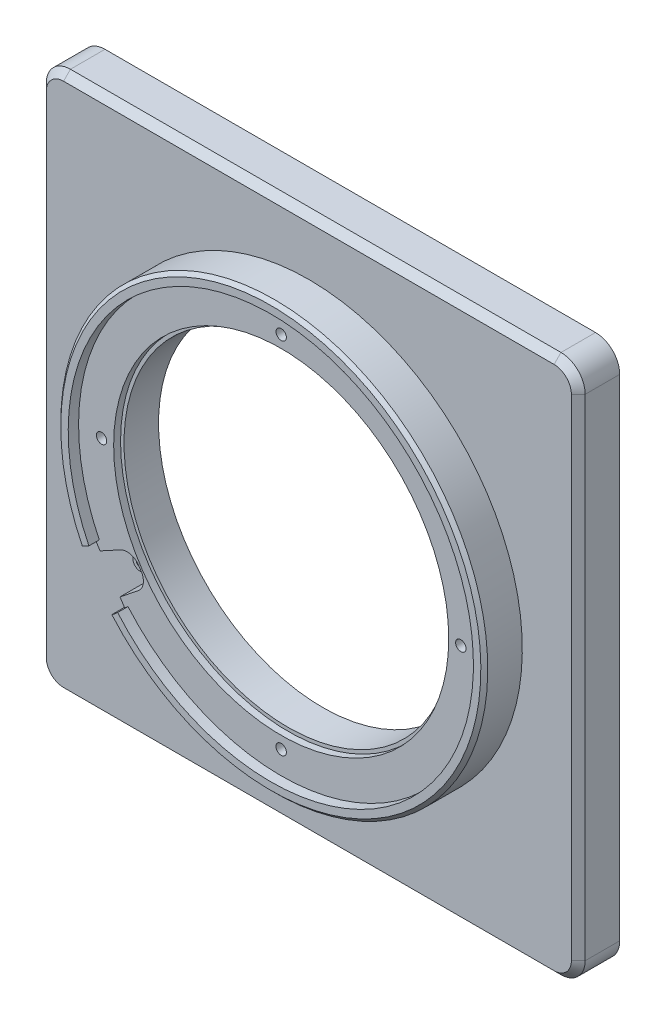
SolidWorks part; units mm, degrees
ref_plane "前视基准面" through (0, 0, 0) normal (0, 0, 1) x (1, 0, 0)
ref_plane "上视基准面" through (0, 0, 0) normal (0, 1, 0) x (1, 0, 0)
ref_plane "右视基准面" through (0, 0, 0) normal (1, 0, 0) x (0, 0, -1)
other "Configuration Table"
sketch "草图1" plane through (0, 0, 0) normal (0, 0, 1) x (1, 0, 0)
  line L1 (-39, -39) -> (39, -39)
  line L2 (-39, -39) -> (-39, 39)
  line L3 (-39, 39) -> (39, 39)
  line L4 (39, -39) -> (39, 39)
  line L5 (-39, -39) -> (39, 39) construction
  line L6 (-39, 39) -> (39, -39) construction
  circle A0 centre (0, 0) radius 23.75
  point P0 (0, 0)
  dimension "D2" = 47.5
  dimension "D1" = 78
extrude "凸台-拉伸1" add sketch "草图1" against normal blind 2
sketch "草图2" plane through (0, 0, 0) normal (0, 0, 1) x (1, 0, 0)
  circle A0 centre (0, 0) radius 23.75
  circle A1 centre (0, 0) radius 23.75 construction
  circle A2 centre (0, 0) radius 30.9
  dimension "D1" = 61.8
extrude "凸台-拉伸2" add sketch "草图2" along normal blind 4
sketch "草图3" plane through (0, 0, -2) normal (0, 0, -1) x (-1, 0, 0)
  line L1 (-39, -39) -> (39, -39)
  line L2 (-39, -39) -> (-39, 39)
  line L3 (-39, 39) -> (39, 39)
  line L4 (39, -39) -> (39, 39)
  line L5 (-39, -39) -> (39, 39) construction
  line L6 (-39, 39) -> (39, -39) construction
  line L7 (-37, -37) -> (37, -37)
  line L8 (-37, -37) -> (-37, 37)
  line L9 (-37, 37) -> (37, 37)
  line L10 (37, -37) -> (37, 37)
  line L11 (-37, -37) -> (37, 37) construction
  line L12 (-37, 37) -> (37, -37) construction
  line L13 (-37, 37) -> (-32, 37)
  line L14 (-37, 37) -> (-37, 32)
  line L15 (-37, 32) -> (-32, 32)
  line L16 (-32, 37) -> (-32, 32)
  line L17 (37, 37) -> (32, 37)
  line L18 (37, 37) -> (37, 32)
  line L19 (37, 32) -> (32, 32)
  line L20 (32, 37) -> (32, 32)
  line L21 (-37, -37) -> (-32, -37)
  line L22 (-37, -37) -> (-37, -32)
  line L23 (-37, -32) -> (-32, -32)
  line L24 (-32, -37) -> (-32, -32)
  line L25 (37, -37) -> (32, -37)
  line L26 (37, -37) -> (37, -32)
  line L27 (37, -32) -> (32, -32)
  line L28 (32, -37) -> (32, -32)
  point P0 (0, 0)
  point P7 (0, 0)
  line M23 (-39, 39) -> (-39, -39)
  line M24 (-39, -39) -> (39, -39)
  line M25 (39, -39) -> (39, 39)
  line M26 (39, 39) -> (-39, 39)
  dimension "D1" = 2
  dimension "D2" = 5
extrude "凸台-拉伸3" add sketch "草图3" along normal blind 4 contours L10 L7 L8 L9 M26 M23 M24 M25 | L16 L9 L8 L15 | L9 L20 L19 L10 | L28 L7 L10 L27 | L7 L24 L23 L8 region at (37.8969, 0, -2) region at (34.5, -34.5, -2) region at (-34.5, -34.5, -2) region at (34.5, 34.5, -2) region at (-34.5, 34.5, -2)
sketch "草图4" plane through (0, 0, 4) normal (0, 0, 1) x (1, 0, 0)
  line L0 (0, 26) -> (0, -26) construction
  line L1 (-26, 0) -> (26, 0) construction
  circle A0 centre (0, 0) radius 26 construction
  circle A1 centre (0, 26) radius 0.75
  circle A2 centre (26, 0) radius 0.75
  circle A3 centre (0, -26) radius 0.75
  circle A4 centre (-26, 0) radius 0.75
  dimension "D2" = 52
  dimension "D3" = 1.5
extrude "切除-拉伸1" cut sketch "草图4" against normal blind 5
sketch "草图5" plane through (0, 0, 4) normal (0, 0, 1) x (1, 0, 0)
  line L0 (-15.4397, 0) -> (13.8511, 0) construction
  line L1 (-27.9748, -13.7193) -> (-23.5593, -20.3904)
  line L2 (-23.5593, -20.3904) -> (0, 0) construction
  line L3 (0, 0) -> (-27.9748, -13.7193) construction
  line L4 (-25.7671, -17.0549) -> (0, 0) construction
  line L5 (-27.9748, -13.7193) -> (-26.8884, -13.1865)
  line L6 (-26.8884, -13.1865) -> (-26.2006, -14.2257)
  line L7 (-26.2006, -14.2257) -> (0, 0) construction
  line L8 (0, 0) -> (-23.3322, -18.5593) construction
  line L9 (-23.3322, -18.5593) -> (-22.6444, -19.5985)
  line L10 (-22.6444, -19.5985) -> (-23.5593, -20.3904)
  line L11 (-26.2006, -14.2257) -> (-23.2413, -12.619)
  line L12 (-20.6192, -13.2728) -> (-20.2742, -13.794)
  line L13 (-20.6969, -16.4631) -> (-23.3322, -18.5593)
  circle A0 centre (0, 0) radius 30.9 construction
  arc A1 (-20.2742, -13.794) -> (-20.6969, -16.4631) centre (-21.942, -14.8979) cw
  arc A2 (-23.2413, -12.619) -> (-20.6192, -13.2728) centre (-22.287, -14.3766) cw
  point P17 (-19.2627, -15.3222)
  point P20 (-21.6307, -11.7445)
  dimension "D6" = 2
  dimension "D1" = 33.5
  dimension "D2" = 8
  dimension "D3" = 5
  dimension "D4" = 1.2
  dimension "D5" = 5.2
extrude "切除-拉伸2" cut sketch "草图5" against normal blind 4
sketch "草图6" plane through (0, 0, 0) normal (0, 0, 1) x (1, 0, 0)
  line L0 (-22.409, -14.8322) -> (0, 0) construction
  line L1 (0, 0) -> (-21.4312, 0) construction
  circle A0 centre (0, 0) radius 26.873 construction
  circle A1 centre (-22.409, -14.8322) radius 0.55
  circle A2 centre (-22.409, -14.8322) radius 1.05
  dimension "D1" = 53.746
  dimension "D3" = 1.1
  dimension "D4" = 2.1
  dimension "D2" = 33.5
extrude "凸台-拉伸4" add sketch "草图6" along normal blind 2
sketch "草图8" plane through (0, 0, 4) normal (0, 0, 1) x (1, 0, 0)
  line L0 (-27.7433, -13.6058) -> (-26.3292, -12.9123)
  line L1 (-23.3644, -20.2217) -> (-22.1735, -19.191)
  circle A0 centre (0, 0) radius 30.9
  circle A1 centre (0, 0) radius 29.325
  arc A2 (-23.3644, -20.2217) -> (-27.7433, -13.6058) centre (0, 0) ccw construction
  line M27 (-27.7433, -13.6058) -> (-26.8884, -13.1865)
  line M35 (-22.6444, -19.5985) -> (-23.3644, -20.2217)
  arc M36 (-23.3644, -20.2217) -> (-27.7433, -13.6058) centre (0, 0) ccw
  dimension "D1" = 58.65
extrude "凸台-拉伸5" add sketch "草图8" along normal blind 1.5 contours A1 L1 L0 M35 M36 M27 region at (-6.7861, 29.2491, 4)
chamfer "倒角1" distance 0.5 angle 45 1 edges at (25.7671, 17.0549, 5.5)
sketch "草图9" plane through (0, 0, -2) normal (0, 0, -1) x (-1, 0, 0)
  line L1 (-19, -19) -> (19, -19) construction
  line L2 (-19, -19) -> (-19, 19) construction
  line L3 (-19, 19) -> (19, 19) construction
  line L4 (19, -19) -> (19, 19) construction
  line L5 (-19, -19) -> (19, 19) construction
  line L6 (-19, 19) -> (19, -19) construction
  circle A0 centre (-19, -19) radius 0.8
  circle A1 centre (-19, -19) radius 1.65
  circle A2 centre (-19, 19) radius 0.8
  circle A3 centre (-19, 19) radius 1.65
  circle A4 centre (19, 19) radius 0.8
  circle A5 centre (19, 19) radius 1.65
  point P0 (0, 0)
  dimension "D2" = 1.6
  dimension "D3" = 3.3
  dimension "D1" = 38
extrude "凸台-拉伸6" add sketch "草图9" along normal blind 2
extrude "切除-拉伸4" cut sketch "草图9<2>" against normal blind 2 contours A2 | A4 | A0 region at (19, -19, -2) region at (19, 19, -2) region at (-19, 19, -2)
sketch "草图9<2>" plane through (0, 0, -2) normal (0, 0, -1) x (-1, 0, 0) same geometry as "草图9"
sketch "草图10" plane through (0, 0, -6) normal (0, 0, -1) x (-1, 0, 0)
  line L0 (39, 39) -> (-39, 39) construction
  line L1 (34.5, -34.5) -> (-34.5, -34.5) construction
  line L2 (34.5, -34.5) -> (34.5, 34.5) construction
  line L3 (34.5, 34.5) -> (-34.5, 34.5) construction
  line L4 (-34.5, -34.5) -> (-34.5, 34.5) construction
  line L5 (34.5, -34.5) -> (-34.5, 34.5) construction
  line L6 (34.5, 34.5) -> (-34.5, -34.5) construction
  circle A0 centre (-34.5, 34.5) radius 0.8
  circle A1 centre (34.5, 34.5) radius 0.8
  circle A2 centre (34.5, -34.5) radius 0.8
  circle A3 centre (-34.5, -34.5) radius 0.8
  point P0 (0, 0)
  dimension "D2" = 1.6
  dimension "D1" = 4.5
extrude "切除-拉伸5" cut sketch "草图10" against normal blind 4
fillet "圆角2" radius 1.5 12 edges at (37, -32, -4) (32, -37, -4) (-32, -37, -4) (-32, -32, -4) (-37, -32, -4) (-37, 32, -4) (-32, 37, -4) (32, -32, -4) (-32, 32, -4) (32, 37, -4) (37, 32, -4) (32, 32, -4)
fillet "圆角3" radius 3.5 4 edges at (39, -39, -3) (-39, -39, -3) (-39, 39, -3) (39, 39, -3)
chamfer "倒角2" distance 1 angle 45 8 edges at (0, -39, 0) (37.9749, -37.9749, 0) (-37.9749, -37.9749, 0) (39, 0, 0) (-39, 0, 0) (37.9749, 37.9749, 0) (-37.9749, 37.9749, 0) (0, 39, 0)
sketch "草图11" plane through (0, 0, 4) normal (0, 0, 1) x (1, 0, 0)
  circle A0 centre (0, 0) radius 24.25
  dimension "D1" = 48.5
extrude "切除-拉伸6" cut sketch "草图11" against normal blind 1
sketch "草图12" plane through (0, 0, -6) normal (0, 0, -1) x (-1, 0, 0)
  line L0 (-30.5, 37) -> (30.5, 37) construction
  line L1 (-25, 37) -> (25, 37)
  line L2 (-25, 37) -> (-25, 38)
  line L3 (-25, 38) -> (25, 38)
  line L4 (25, 37) -> (25, 38)
  line L5 (37, -30.5) -> (37, 30.5) construction
  line L6 (37, 25) -> (38, 25)
  line L7 (37, 25) -> (37, -25)
  line L8 (37, -25) -> (38, -25)
  line L9 (38, 25) -> (38, -25)
  line L10 (-30.5, -37) -> (30.5, -37) construction
  line L11 (25, -37) -> (-25, -37)
  line L12 (25, -37) -> (25, -38)
  line L13 (25, -38) -> (-25, -38)
  line L14 (-25, -37) -> (-25, -38)
  line L15 (-37, -30.5) -> (-37, 30.5) construction
  line L16 (-37, -25) -> (-38, -25)
  line L17 (-37, -25) -> (-37, 25)
  line L18 (-37, 25) -> (-38, 25)
  line L19 (-38, -25) -> (-38, 25)
  line L20 (0, -4.6052) -> (0, 11.8131) construction
  line L21 (-9.8593, 0) -> (12.3811, 0) construction
  dimension "D1" = 50
  dimension "D2" = 1
extrude "切除-拉伸7" cut sketch "草图12" against normal blind 1
